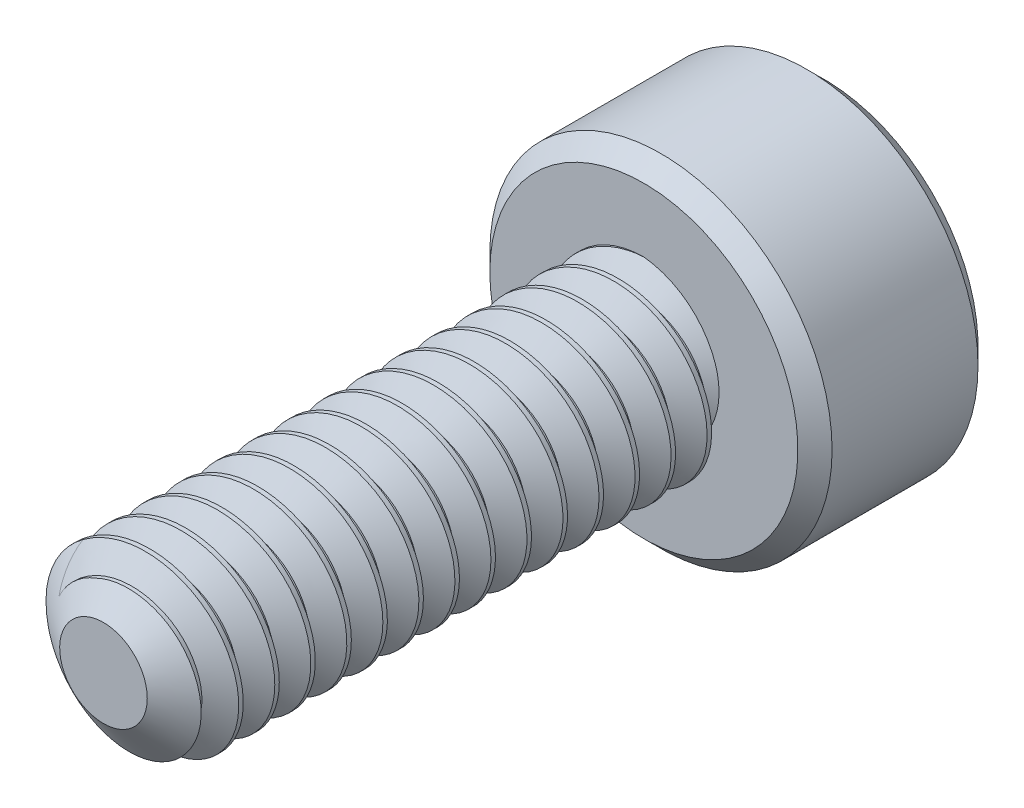
SolidWorks part; units mm, degrees
ref_plane "Front Plane" through (0, 0, 0) normal (0, 0, 1) x (1, 0, 0)
ref_plane "Top Plane" through (0, 0, 0) normal (0, 1, 0) x (1, 0, 0)
ref_plane "Right Plane" through (0, 0, 0) normal (1, 0, 0) x (0, 0, -1)
sketch "Shaft Sketch" plane through (0, 0, 0) normal (0, 0, 1) x (1, 0, 0)
  circle A0 centre (0, 0) radius 1
  dimension "OD" = 2
extrude "Shaft Extrude" add sketch "Shaft Sketch" against normal blind 6
sketch "Thread Spiral Sketch" plane through (0, 0, 0) normal (0, 0, 1) x (1, 0, 0)
  circle A0 centre (0, 0) radius 1 construction
  circle A1 centre (0, 0) radius 1
curve "Thread Helix/Spiral" pitch 0.4 height 6.4 radius 1 centre (0, 0, 0) axis (0, 0, -1) start towards (0, 1, 0) parameters "pitch"=0.4
sketch "Thread Cut Sketch" plane through (0, 0, 0) normal (1, 0, 0) x (0, 0, -1)
  line L0 (-0.35, 1) -> (-0.2, 0.7402)
  line L1 (-0.2, 0.7402) -> (-0.15, 0.7402)
  line L2 (-0.15, 0.7402) -> (0, 1)
  line L3 (-0.35, 1) -> (0, 1)
  line L4 (-0.175, 1) -> (-0.175, 0.7402) construction
  line L5 (-0.275, 0.8701) -> (-0.075, 0.8701) construction
  line L6 (0, 1) -> (0, -1) construction
  dimension "D1" = 0.05
  dimension "D2" = 0.2
  dimension "D3" = 60
sweep "Thread Cut Sweep" cut profiles "Thread Cut Sketch" path "Thread Helix/Spiral" align with end faces yes
sketch "End Chamfer Sketch" plane through (0, 0, 0) normal (1, 0, 0) x (0, 0, -1)
  line L0 (0.3598, 1) -> (0, 0.4862)
  line L1 (0, 0.4862) -> (0, 1)
  line L2 (0.3598, 1) -> (0, 1)
  line L3 (-0.35, 1) -> (0, 1) construction
  line L4 (0, 0) -> (7.0209, 0) construction
  dimension "D1" = 55
  dimension "D2" = 0.254
revolve "End Chamfer Revolve" cut sketch "End Chamfer Sketch" angle 360 about L4
sketch "Head Extrude Sketch" plane through (0, 0, -6) normal (0, 0, -1) x (-1, 0, 0)
  circle A0 centre (0, 0) radius 1.9
  dimension "head dia" = 3.8
extrude "Head Extrude" add sketch "Head Extrude Sketch" along normal blind 2
sketch "Sketch7" plane through (0, 0, -8) normal (0, 0, -1) x (-1, 0, 0)
  line L1 (0, 0.866) -> (-0.75, 0.433)
  line L2 (-0.75, 0.433) -> (-0.75, -0.433)
  line L3 (-0.75, -0.433) -> (0, -0.866)
  line L4 (0, -0.866) -> (0.75, -0.433)
  line L5 (0.75, -0.433) -> (0.75, 0.433)
  line L6 (0.75, 0.433) -> (0, 0.866)
  circle A0 centre (0, 0) radius 0.75 construction
  dimension "hex dia" = 1.5
extrude "Socket Cut Extrude" cut sketch "Sketch7" against normal blind 1.125
sketch "Socket Entry Sketch" plane through (0, 0, -8) normal (0, 0, -1) x (-1, 0, 0)
  circle A0 centre (0, 0) radius 0.866
extrude "Socket Entry Cut Extrude" cut sketch "Socket Entry Sketch" against normal through all draft 45
chamfer "Head Chamfer" distance 0.19 angle 45 2 edges at (-1.9, 0, -8) (-1.9, 0, -6)
sketch "Sketch10" plane through (0, 0, -6) normal (0, 0, 1) x (1, 0, 0)
  circle A1 centre (0, 0) radius 1
  circle A2 centre (0, 0) radius 1
  dimension "D1" = 0
ref_plane "Partial Thread Plane" through (0, 0, -17) normal (0, 0, 1) x (1, 0, 0)
extrude "Partial Thread Extrude" [suppressed] add sketch "Sketch10" along normal up to surface (1 mm away) separate body up to plane "Partial Thread Plane"
chamfer "Partial Thread Chamfer" [suppressed] distance 0.04 angle 45
combine bodies "Partial Thread Combine" [suppressed] operation type add bodies to combine 107 108
equation "\"D3@Thread Helix/Spiral\" = \"screw length@Shaft Extrude\" + \"pitch@Thread Helix/Spiral\""
equation "\"D1@Thread Cut Sketch\" = \"pitch@Thread Helix/Spiral\" * .125"
equation "\"D2@Thread Cut Sketch\" = \"pitch@Thread Helix/Spiral\" * .5"
equation "\"D1@Socket Cut Extrude\" = \"hex dia@Sketch7\" * .75"
equation "\"D1@Head Chamfer\" = \"head dia@Head Extrude Sketch\" * .05"
equation "\"D1@Partial Thread Chamfer\" = \"OD@Shaft Sketch\" * .02"
equation "\"Screw Diameter\"= 2mm"
equation "\"Thread Pitch\"= 0.4mm"
equation "\"Head Height\"= 2mm"
equation "\"Hex Size\"= 1.5mm"
equation "\"Head Diameter\"= 3.8mm"
equation "\"OD@Shaft Sketch\"=\"Screw Diameter\""
equation "\"pitch@Thread Helix/Spiral\"=\"Thread Pitch\""
equation "\"head dia@Head Extrude Sketch\"=\"Head Diameter\""
equation "\"head depth@Head Extrude\"=\"Head Height\""
